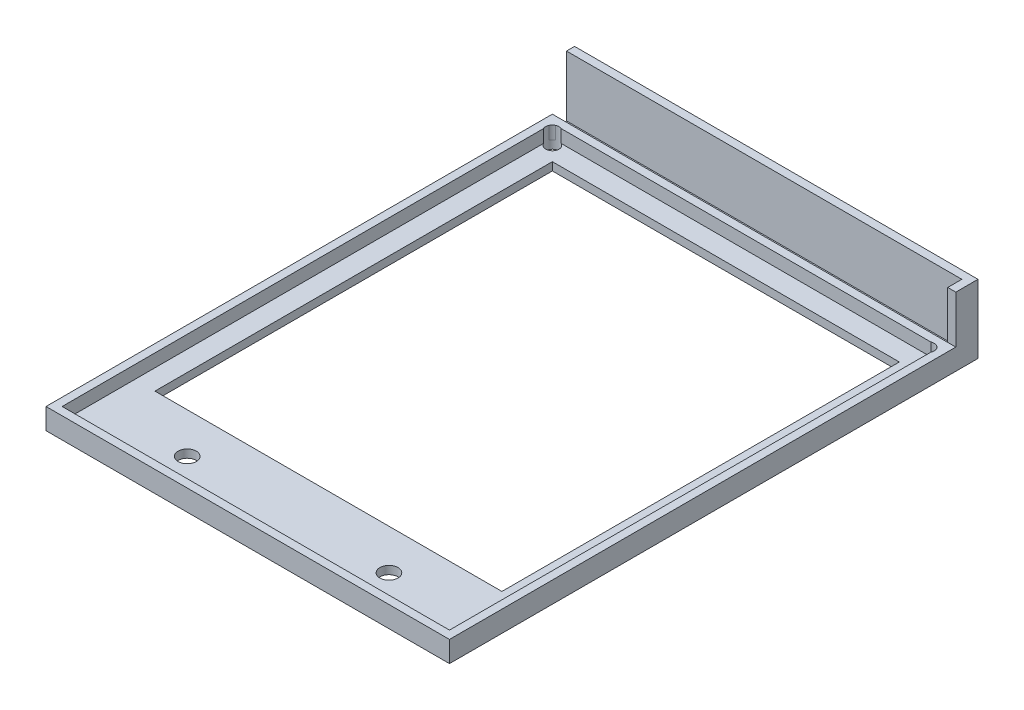
SolidWorks part; units mm, degrees
ref_plane "Front Plane" through (0, 0, 0) normal (0, 0, 1) x (1, 0, 0)
ref_plane "Top Plane" through (0, 0, 0) normal (0, 1, 0) x (1, 0, 0)
ref_plane "Right Plane" through (0, 0, 0) normal (1, 0, 0) x (0, 0, -1)
sketch "Sketch1" plane through (0, 0, 0) normal (0, 1, 0) x (1, 0, 0)
  line L1 (-48, -60.75) -> (48, -60.75)
  line L2 (-48, -60.75) -> (-48, 60.75)
  line L3 (-48, 60.75) -> (48, 60.75)
  line L4 (48, -60.75) -> (48, 60.75)
  line L5 (-48, -60.75) -> (48, 60.75) construction
  line L6 (-48, 60.75) -> (48, -60.75) construction
  line L11 (-43, 55.75) -> (43, 55.75)
  line L12 (-43, 55.75) -> (-43, -42.75)
  line L13 (-43, -42.75) -> (43, -42.75)
  line L14 (43, 55.75) -> (43, -42.75)
  point P0 (0, 0)
  point P6 (0, 0)
  dimension "D1" = 96
  dimension "D2" = 121.5
  dimension "D3" = 18
  dimension "D4" = 5
  dimension "D5" = 5
  dimension "D6" = 5
extrude "Boss-Extrude1" add sketch "Sketch1" along normal blind 2
sketch "Sketch2" plane through (0, 0, 0) normal (0, 1, 0) x (1, 0, 0)
  line L1 (-50, -62.75) -> (50, -62.75)
  line L2 (-50, -62.75) -> (-50, 62.75)
  line L3 (-50, 62.75) -> (50, 62.75)
  line L4 (50, -62.75) -> (50, 62.75)
  line L5 (-50, -62.75) -> (50, 62.75) construction
  line L6 (-50, 62.75) -> (50, -62.75) construction
  line L7 (-48, 60.75) -> (48, 60.75)
  line L8 (-48, 60.75) -> (-48, -60.75)
  line L9 (-48, -60.75) -> (48, -60.75)
  line L10 (48, 60.75) -> (48, -60.75)
  point P0 (0, 0)
  dimension "D1" = 2
  dimension "D2" = 2
extrude "Boss-Extrude2" add sketch "Sketch2" along normal blind 5.2
sketch "Sketch3" plane through (0, 0, 0) normal (0, -1, 0) x (1, 0, 0)
  line L0 (0, 42.75) -> (0, 62.75) construction
  line L1 (-43, 42.75) -> (43, 42.75) construction
  line L2 (-50, 62.75) -> (50, 62.75) construction
  line L3 (0, 52.75) -> (50, 52.75) construction
  line L4 (50, 62.75) -> (50, -62.75) construction
  line L5 (50, -62.75) -> (43, -55.75) construction
  circle A0 centre (25, 52.75) radius 2.25
  circle A1 centre (-25, 52.75) radius 2.25
  circle A2 centre (46.5, -59.25) radius 1.65
  circle A3 centre (-46.5, -59.25) radius 1.65
  dimension "D1" = 4.5
  dimension "D2" = 3.3
extrude "Cut-Extrude1" cut sketch "Sketch3" against normal up to next and the other way through all
fillet "Fillet1" radius 1.65 2 edges at (48, 3.6, -60.75) (-48, 3.6, -60.75)
sketch "Sketch4" plane through (0, 0, 0) normal (0, 1, 0) x (1, 0, 0)
  line L0 (50, 62.75) -> (50, 68.25) construction
  line L1 (-50, 62.75) -> (50, 62.75)
  line L2 (-50, 62.75) -> (-50, 68.25)
  line L3 (-50, 68.25) -> (50, 68.25)
  line L4 (50, 62.75) -> (50, 68.25)
  dimension "D1" = 5.5
extrude "Boss-Extrude3" add sketch "Sketch4" along normal blind 2
sketch "Sketch7" plane through (0, 2, 0) normal (0, 1, 0) x (1, 0, 0)
  line L0 (50, 62.75) -> (50, 68.25) construction
  line L1 (-50, 68.25) -> (50, 68.25)
  line L2 (-50, 68.25) -> (-50, 66.25)
  line L3 (-50, 66.25) -> (48, 66.25)
  line L4 (50, 68.25) -> (50, 62.75)
  line L6 (50, 62.75) -> (48, 62.75)
  line L9 (48, 62.75) -> (48, 66.25)
  dimension "D1" = 2
  dimension "D2" = 2
extrude "Boss-Extrude5" add sketch "Sketch7" along normal blind 15
